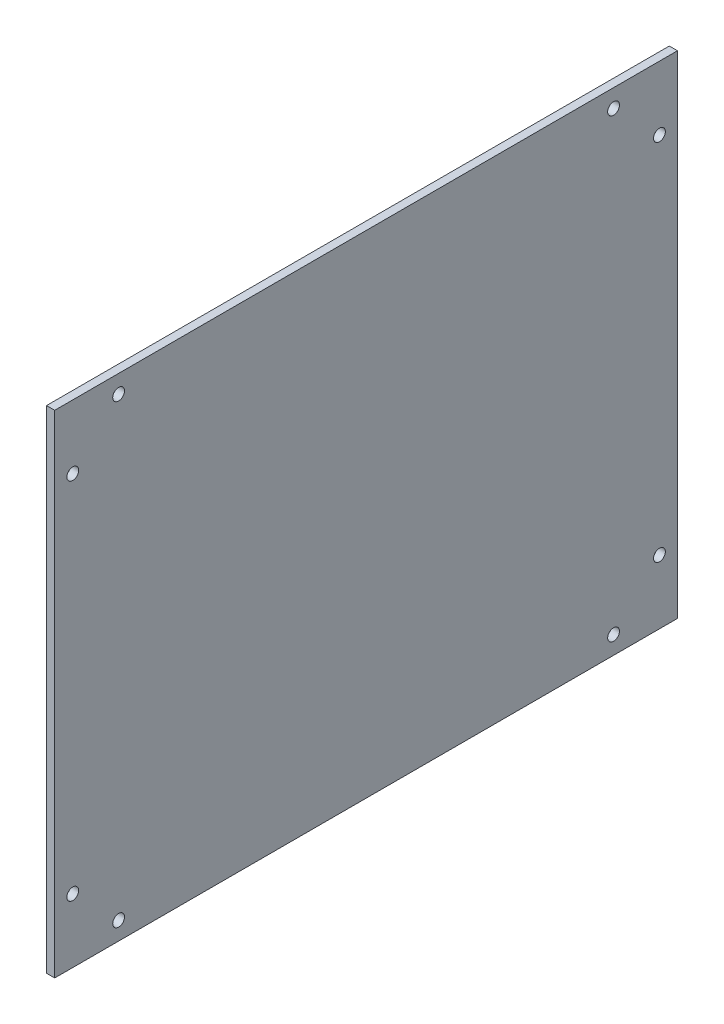
SolidWorks part; units mm, degrees
ref_plane "Front Plane" through (0, 0, 0) normal (0, 0, 1) x (1, 0, 0)
ref_plane "Top Plane" through (0, 0, 0) normal (0, 1, 0) x (1, 0, 0)
ref_plane "Right Plane" through (0, 0, 0) normal (1, 0, 0) x (0, 0, -1)
sketch "Sketch1" plane through (0, 0, 0) normal (1, 0, 0) x (0, 0, -1)
  line L1 (0, 0) -> (241.3, 0)
  line L2 (0, 0) -> (0, 190.5)
  line L3 (0, 190.5) -> (241.3, 190.5)
  line L4 (241.3, 0) -> (241.3, 190.5)
  dimension "D1" = 241.3
  dimension "D2" = 190.5
extrude "Boss-Extrude1" add sketch "Sketch1" along normal blind 3.175
sketch "Sketch2" plane through (3.175, 0, 0) normal (1, 0, 0) x (0, 0, -1)
  line L0 (241.3, 0) -> (241.3, 190.5) construction
  line L1 (0, 0) -> (241.3, 0) construction
  line L2 (-1000, 95.25) -> (49000, 95.25) construction
  line L3 (0, 190.5) -> (0, 0) construction
  line L4 (120.65, -809.5) -> (120.65, 49190.5) construction
  line L5 (241.3, 190.5) -> (0, 190.5) construction
  line L6 (1228.6, 95.25) -> (-48771.4, 95.25) construction
  circle A0 centre (216.535, 6.985) radius 2.286
  circle A1 centre (234.315, 24.765) radius 2.286
  circle A2 centre (234.315, 165.735) radius 2.286
  circle A3 centre (216.535, 183.515) radius 2.286
  circle A4 centre (24.765, 183.515) radius 2.286
  circle A5 centre (6.985, 165.735) radius 2.286
  circle A6 centre (6.985, 24.765) radius 2.286
  circle A7 centre (24.765, 6.985) radius 2.286
  point P15 (0, 95.25)
  point P20 (120.65, 190.5)
  dimension "D1" = 4.572
  dimension "D2" = 6.985
  dimension "D3" = 24.765
  dimension "D4" = 6.985
  dimension "D5" = 24.765
extrude "Cut-Extrude1" cut sketch "Sketch2" against normal through all
